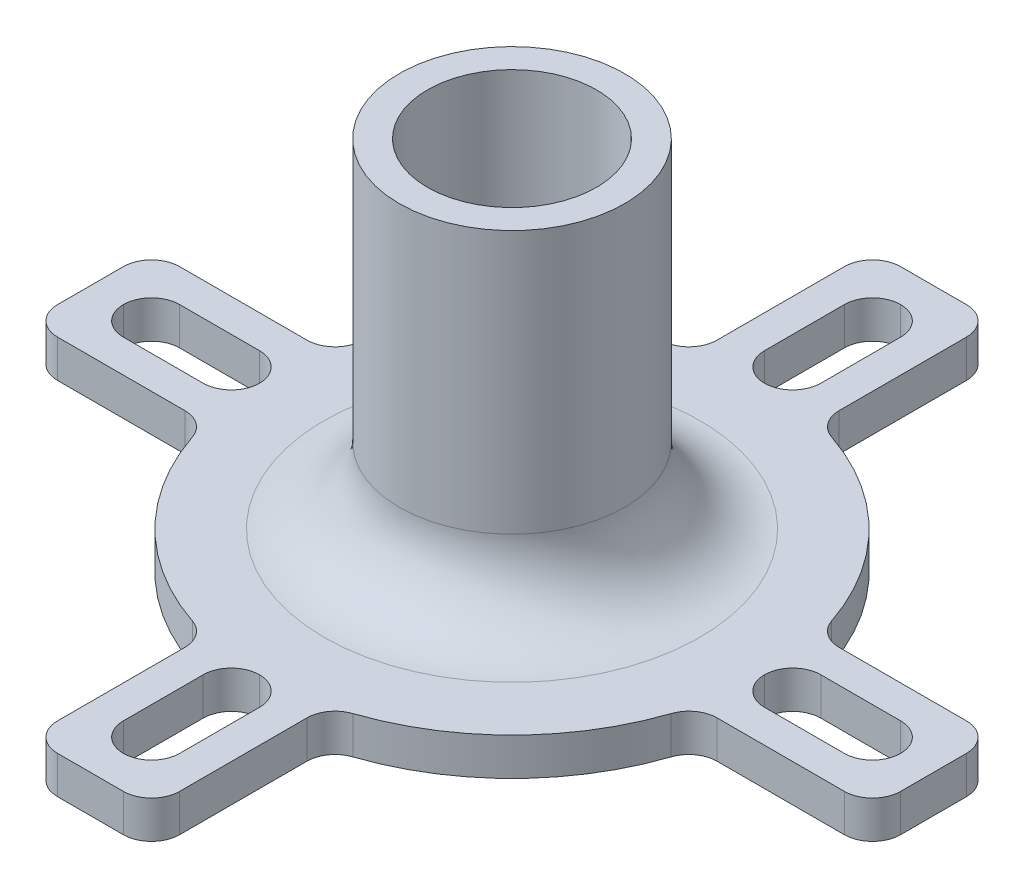
SolidWorks part; units mm, degrees
ref_plane "Front Plane" through (0, 0, 0) normal (0, 0, 1) x (1, 0, 0)
ref_plane "Top Plane" through (0, 0, 0) normal (0, 1, 0) x (1, 0, 0)
ref_plane "Right Plane" through (0, 0, 0) normal (1, 0, 0) x (0, 0, -1)
sketch "Sketch1" plane through (0, 0, 0) normal (0, 1, 0) x (1, 0, 0)
  circle A0 centre (0, 0) radius 13.4428
  dimension "D1" = 26.8856
extrude "Boss-Extrude1" add sketch "Sketch1" along normal blind 2
sketch "Sketch2" plane through (0, 2, 0) normal (0, 1, 0) x (1, 0, 0)
  line L0 (0, 0) -> (0, 13.4428) construction
  line L1 (3.25, 4.4428) -> (-3.25, 4.4428)
  line L2 (3.25, 4.4428) -> (3.25, 22.4428)
  line L3 (3.25, 22.4428) -> (-3.25, 22.4428)
  line L4 (-3.25, 4.4428) -> (-3.25, 22.4428)
  line L5 (3.25, 4.4428) -> (-3.25, 22.4428) construction
  line L6 (3.25, 22.4428) -> (-3.25, 4.4428) construction
  line L8 (1.5, 6.1928) -> (-1.5, 6.1928)
  line L9 (1.5, 6.1928) -> (1.5, 20.6928)
  line L10 (1.5, 20.6928) -> (-1.5, 20.6928)
  line L11 (-1.5, 6.1928) -> (-1.5, 20.6928)
  line L12 (1.5, 6.1928) -> (-1.5, 20.6928) construction
  line L13 (1.5, 20.6928) -> (-1.5, 6.1928) construction
  circle A0 centre (0, 0) radius 13.4428 construction
  point P0 (0, 13.4428)
  dimension "D1" = 18
  dimension "D2" = 6.5
  dimension "D3" = 3
  dimension "D4" = 14.5
extrude "Boss-Extrude3" add sketch "Sketch2" against normal blind 2
fillet "Fillet1" radius 1.5 8 edges at (3.25, 1, -13.044) (3.25, 1, -22.4428) (-3.25, 1, -22.4428) (-3.25, 1, -13.044) (-1.5, 1, -13.3589) (1.5, 1, -13.3589) (1.5, 1, -20.6928) (-1.5, 1, -20.6928)
ref_axis "Axis1" through (0, -0.1, 0) along (0, 1, 0)
pattern_circular "CirPattern1" count 4 over 360 about axis through (0, -0.1, 0) along (0, 1, 0) of "Boss-Extrude3", "Fillet1"
sketch "Sketch3" plane through (0, 2, 0) normal (0, 1, 0) x (1, 0, 0)
  circle A0 centre (0, 0) radius 4.5
  circle A1 centre (0, 0) radius 6
  dimension "D1" = 9
  dimension "D2" = 1.5
extrude "Boss-Extrude4" add sketch "Sketch3" along normal blind 18
fillet "Fillet2" radius 4 1 edges at (0, 2, 6)
